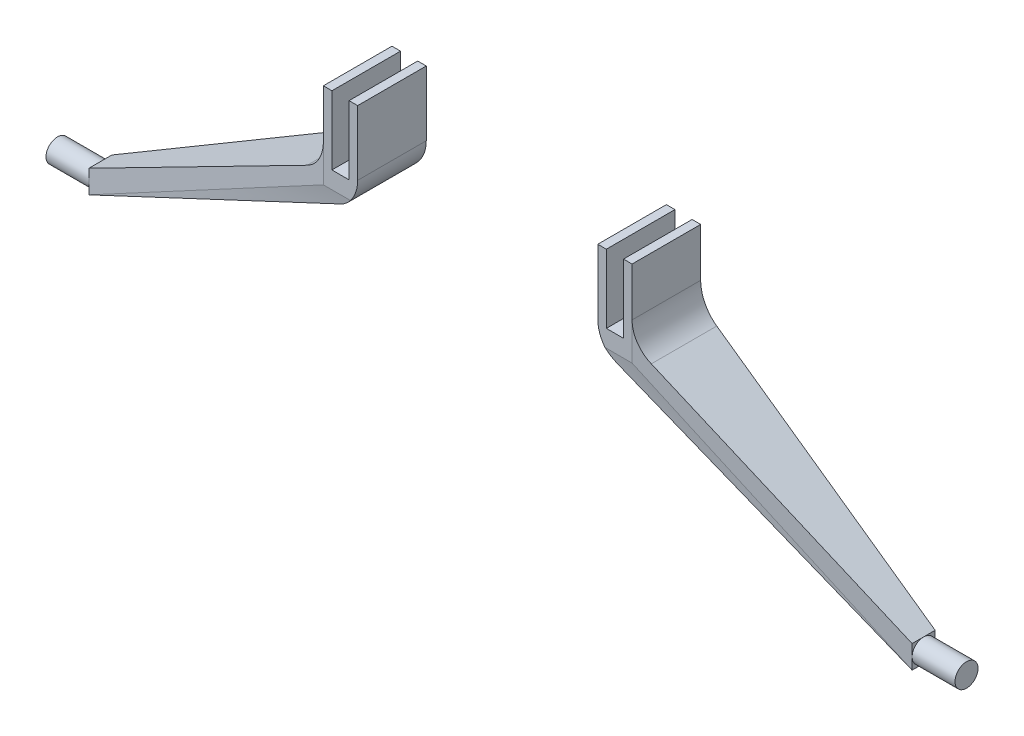
SolidWorks part; units mm, degrees
note: The reader was unsure of these and kept them because the rebuilt part matched: shared geometry of "Sketch5<2>".
ref_plane "Front Plane" through (0, 0, 0) normal (0, 0, 1) x (1, 0, 0)
ref_plane "Top Plane" through (0, 0, 0) normal (0, 1, 0) x (1, 0, 0)
ref_plane "Right Plane" through (0, 0, 0) normal (1, 0, 0) x (0, 0, -1)
sketch "A1 Bed Dimensions" plane through (0, 0, 0) normal (0, 0, 1) x (1, 0, 0)
  line L1 (-204.0103, -79.9047) -> (-24.0103, -79.9047) construction
  line L2 (-204.0103, -79.9047) -> (-204.0103, 100.0953) construction
  line L3 (-204.0103, 100.0953) -> (-24.0103, 100.0953) construction
  line L4 (-24.0103, -79.9047) -> (-24.0103, 100.0953) construction
  line L5 (-204.0103, -79.9047) -> (-24.0103, 100.0953) construction
  line L6 (-204.0103, 100.0953) -> (-24.0103, -79.9047) construction
  point P0 (0, 0)
  dimension "D1" = 180
  dimension "D2" = 180
sketch "Sketch3" plane through (0, 0, 0) normal (0, 0, 1) x (1, 0, 0)
  line L13 (-44.45, 50.8) -> (-44.45, 82.55)
  line L14 (-44.45, 82.55) -> (-47.625, 82.55)
  line L16 (-47.625, 82.55) -> (-47.625, 57.15)
  line L17 (-47.625, 57.15) -> (-53.975, 57.15)
  line L18 (-53.975, 57.15) -> (-53.975, 82.55)
  line L19 (-53.975, 82.55) -> (-57.15, 82.55)
  line L20 (-57.15, 82.55) -> (-57.15, 50.8)
  line L21 (-57.15, 50.8) -> (-44.45, 50.8)
  dimension "D1" = 3.175
  dimension "D2" = 44.45
  dimension "D3" = 50.8
  dimension "D4" = 6.35
  dimension "D5" = 6.35
  dimension "D7" = 25.4
  dimension "D8" = 3.175
extrude "Boss-Extrude1" add sketch "Sketch3" along normal blind 25.4
ref_plane "Landing Gear Width" through (-152.4, 0, 0) normal (1, 0, 0) x (0, 0, -1)
sketch "Sketch5" plane through (-152.4, 0, 0) normal (1, 0, 0) x (0, 0, -1)
  line L0 (-25.4, 50.8) -> (0, 50.8) construction
  line L1 (-16.9625, 4.2625) -> (-8.4375, 4.2625)
  line L2 (-16.9625, 4.2625) -> (-16.9625, -4.2625)
  line L3 (-16.9625, -4.2625) -> (-8.4375, -4.2625)
  line L4 (-8.4375, 4.2625) -> (-8.4375, -4.2625)
  point P4 (-8.4375, 0)
  point P9 (-12.7, 50.8)
  point P10 (-12.7, 4.2625)
  dimension "D1" = 8.525
  dimension "D2" = 8.525
loft "Loft1" add profiles "Sketch5" section face at (-50.8, 50.8, 12.7) section "Sketch5"
sketch "Sketch6" plane through (-57.15, 0, 0) normal (-1, 0, 0) x (0, 0, 1)
  line L0 (25.4, 82.55) -> (25.4, 50.8) construction
  line L1 (0, 50.8) -> (25.4, 50.8)
  line L2 (0, 50.8) -> (0, 57.15)
  line L3 (0, 57.15) -> (25.4, 57.15)
  line L4 (25.4, 50.8) -> (25.4, 57.15)
  dimension "D1" = 6.35
loft "Loft2" add profiles "Sketch6", "Sketch5<2>"
sketch "Sketch5<2>" plane through (-152.4, 0, 0) normal (1, 0, 0) x (0, 0, -1) same geometry as "Sketch5"
fillet "Fillet2" radius 12.7 1 edges
fillet "Fillet3" radius 12.7 1 edges at (-44.45, 50.8, 12.7)
sketch "Sketch7" plane through (-152.4, 0, 0) normal (-1, 0, 0) x (0, 0, 1)
  line L0 (16.9625, -4.2625) -> (8.4375, -4.2625) construction
  line L1 (16.9625, 4.2625) -> (16.9625, -4.2625) construction
  line L2 (8.4375, 4.2625) -> (16.9625, 4.2625) construction
  circle A0 centre (12.7, 0) radius 4.2625
extrude "Boss-Extrude3" add sketch "Sketch7" along normal blind 15.875
mirror "Mirror2" about plane through (0, 0, 0) normal (1, 0, 0) of bodies 106
